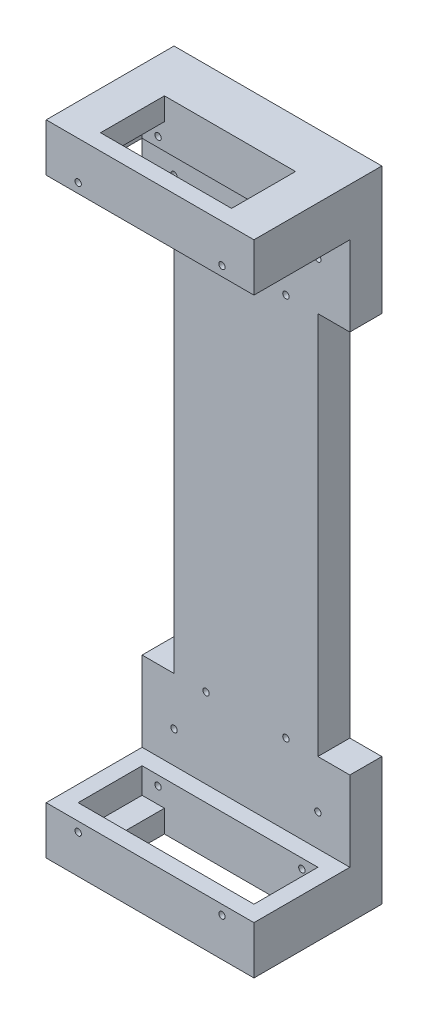
SolidWorks part; units mm, degrees
ref_plane "Plan de face" through (0, 0, 0) normal (0, 0, 1) x (1, 0, 0)
ref_plane "Plan de dessus" through (0, 0, 0) normal (0, 1, 0) x (1, 0, 0)
ref_plane "Plan de droite" through (0, 0, 0) normal (1, 0, 0) x (0, 0, -1)
sketch "Esquisse1" plane through (0, 0, 0) normal (0, 0, 1) x (1, 0, 0)
  line L0 (-10, -50) -> (-10, -40) construction
  line L1 (0, 0) -> (-65, 0)
  line L2 (0, 0) -> (0, -200)
  line L3 (0, -200) -> (-65, -200)
  line L4 (-65, 0) -> (-65, -200)
  line L5 (-55, -50) -> (-55, -40) construction
  line L6 (-10, -50) -> (-55, -50) construction
  line L7 (-10, -40) -> (0, -40) construction
  line L8 (-65, -40) -> (-55, -40) construction
  line L9 (-55, -150) -> (-10, -150) construction
  line L10 (-10, -150) -> (-10, -160) construction
  line L11 (-55, -150) -> (-55, -160) construction
  line L12 (-10, -160) -> (0, -160) construction
  line L13 (-55, -160) -> (-65, -160) construction
  circle A0 centre (-55, -25) radius 1
  circle A1 centre (-45, -40) radius 1
  circle A2 centre (-20, -40) radius 1
  circle A3 centre (-10, -25) radius 1
  circle A4 centre (-45, -160) radius 1
  circle A5 centre (-20, -160) radius 1
  circle A6 centre (-10, -175) radius 1
  circle A7 centre (-55, -175) radius 1
  dimension "D11" = 2
  dimension "D12" = 2
  dimension "D13" = 2
  dimension "D14" = 2
  dimension "D19" = 2
  dimension "D20" = 2
  dimension "D23" = 2
  dimension "D26" = 2
  dimension "D1" = 65
  dimension "D2" = 200
  dimension "D3" = 10
  dimension "D4" = 10
  dimension "D5" = 10
  dimension "D6" = 10
  dimension "D7" = 10
  dimension "D8" = 10
  dimension "D9" = 15
  dimension "D10" = 15
  dimension "D15" = 10
  dimension "D16" = 10
  dimension "D17" = 10
  dimension "D18" = 10
  dimension "D21" = 10
  dimension "D22" = 15
  dimension "D24" = 15
  dimension "D25" = 10
extrude "Boss.-Extru.1" add sketch "Esquisse1" along normal blind 10
sketch "Esquisse2" plane through (0, 0, 10) normal (0, 0, 1) x (1, 0, 0)
  line L5 (0, 0) -> (-65, 0)
  line L6 (0, 0) -> (0, -15)
  line L7 (0, -15) -> (-65, -15)
  line L8 (-65, 0) -> (-65, -15)
  line L9 (0, -200) -> (-65, -200)
  line L10 (0, -200) -> (0, -185)
  line L11 (0, -185) -> (-65, -185)
  line L12 (-65, -200) -> (-65, -185)
  dimension "D1" = 65
  dimension "D2" = 15
extrude "Boss.-Extru.2" add sketch "Esquisse2" along normal blind 30
sketch "Esquisse3" plane through (0, -200, 0) normal (0, -1, 0) x (1, 0, 0)
  line L5 (-53, 35) -> (-12, 35)
  line L6 (-53, 35) -> (-53, 15)
  line L7 (-53, 15) -> (-12, 15)
  line L8 (-12, 35) -> (-12, 15)
  line L13 (-65, 35) -> (-53, 35) construction
  line L17 (-65, 40) -> (-65, 0) construction
  line L18 (-53, 40) -> (-53, 35) construction
  line L19 (-65, 40) -> (0, 40) construction
  line L20 (-12, 40) -> (-12, 35) construction
  line L21 (0, 35) -> (-12, 35) construction
  line L22 (0, 40) -> (0, 0) construction
extrude "Enlèv. mat.-Extru.1" cut sketch "Esquisse3" against normal through all
sketch "Esquisse4" plane through (0, -15, 0) normal (0, -1, 0) x (1, 0, 0)
  line L8 (-12, 35) -> (-53, 35) construction
  line L9 (-60, 35) -> (-5, 35)
  line L10 (-60, 35) -> (-60, 15)
  line L11 (-60, 15) -> (-5, 15)
  line L12 (-5, 35) -> (-5, 15)
  line L13 (-53, 15) -> (-12, 15) construction
  line L14 (-65, 40) -> (-65, 0) construction
  line L15 (0, 40) -> (0, 0) construction
  dimension "D3" = 5
  dimension "D4" = 5
extrude "Enlèv. mat.-Extru.2" cut sketch "Esquisse4" against normal blind 8 and the other way blind 178
sketch "Esquisse5" plane through (0, 0, 40) normal (0, 0, 1) x (1, 0, 0)
  line L7 (-65, -188) -> (-55, -188)
  line L8 (-65, -185) -> (-65, -200) construction
  line L9 (-55, -188) -> (-55, -185)
  line L10 (0, -185) -> (-65, -185) construction
  line L11 (-10, -185) -> (-10, -188)
  line L12 (-10, -188) -> (0, -188)
  line L13 (0, -200) -> (0, -185) construction
  line L14 (-10, -12) -> (-10, -15)
  line L15 (-65, -15) -> (0, -15) construction
  line L16 (-10, -12) -> (0, -12)
  line L17 (0, -15) -> (0, 0) construction
  line L18 (-65, -12) -> (-55, -12)
  line L19 (-65, -185) -> (-65, -15) construction
  line L20 (-55, -12) -> (-55, -15)
  line L21 (-65, -15) -> (0, -15) construction
  circle A1 centre (-55, -12) radius 1
  circle A2 centre (-10, -12) radius 1
  circle A3 centre (-10, -188) radius 1
  circle A4 centre (-55, -188) radius 1
  dimension "D1" = 10
  dimension "D2" = 3
  dimension "D3" = 2
  dimension "D4" = 2
  dimension "D5" = 2
  dimension "D6" = 2
extrude "Enlèv. mat.-Extru.3" cut sketch "Esquisse5" against normal through all contours L7 A4 L9 | L11 A3 L12 | L12 A3 L11 | L9 A4 L7 | A1 | A2 region at (-55.4244, -187.5756, 40) region at (-54.8585, -188.1415, 40) region at (-9.5756, -187.5756, 40) region at (-10.1415, -188.1415, 40)
sketch "Esquisse6" plane through (0, 0, 10) normal (0, 0, 1) x (1, 0, 0)
  line L0 (-55, -40) -> (-10, -40)
  line L1 (-55, -40) -> (-55, -160)
  line L2 (-10, -40) -> (-10, -160)
  line L3 (-55, -160) -> (-10, -160)
  line L4 (0, -185) -> (-65, -185) construction
  line L5 (-65, -15) -> (0, -15) construction
  line L6 (-65, -15) -> (-65, -185) construction
  line L7 (0, -185) -> (0, -15) construction
  line L8 (-55, -40) -> (-65, -40)
  line L9 (-55, -40) -> (-55, -160)
  line L10 (-65, -40) -> (-65, -160)
  line L11 (-55, -160) -> (-65, -160)
  line L12 (-10, -160) -> (0, -160)
  line L13 (-10, -160) -> (-10, -40)
  line L14 (0, -160) -> (0, -40)
  line L15 (-10, -40) -> (0, -40)
  line M14 (0, -185) -> (0, -15)
  line M16 (-65, -15) -> (-65, -185)
  dimension "D1" = 25
  dimension "D2" = 25
  dimension "D3" = 10
  dimension "D4" = 10
extrude "Enlèv. mat.-Extru.4" cut sketch "Esquisse6" against normal blind 10 contours L11 L1 L8 M16 | L15 L2 L12 M14 region at (-60, -100, 10) region at (-5, -100, 10)
